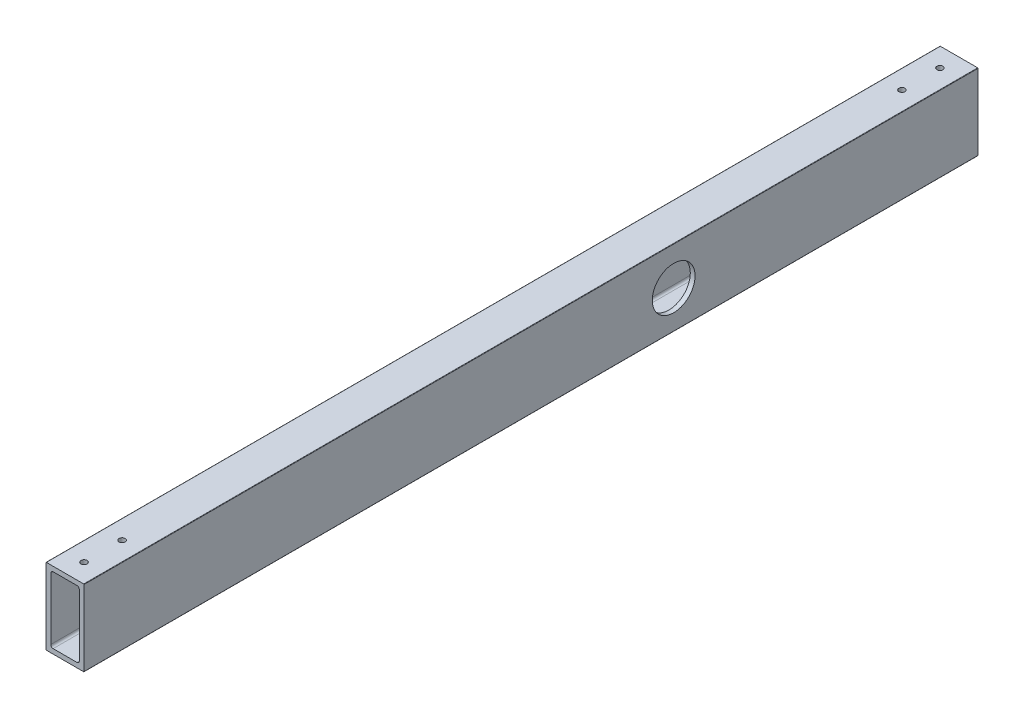
SolidWorks part; units mm, degrees
material "3.0205 (EN-AW 1200)"
ref_plane "Front Plane" through (0, 0, 0) normal (0, 0, 1) x (1, 0, 0)
ref_plane "Top Plane" through (0, 0, 0) normal (0, 1, 0) x (1, 0, 0)
ref_plane "Right Plane" through (0, 0, 0) normal (1, 0, 0) x (0, 0, -1)
ref_plane "Plane1" through (0, 0, 0) normal (0, 0, -1) x (-1, 0, 0)
sketch "Sketch1" plane through (0, 0, 0) normal (0, 0, -1) x (-1, 0, 0)
  line L0 (-3.175, 46.0375) -> (-3.175, 4.7625)
  line L1 (-4.7625, 3.175) -> (-20.6375, 3.175)
  line L2 (-22.225, 4.7625) -> (-22.225, 46.0375)
  line L3 (-20.6375, 47.625) -> (-4.7625, 47.625)
  line L4 (0, 0.254) -> (0, 50.546)
  line L5 (-0.254, 50.8) -> (-25.146, 50.8)
  line L6 (-25.4, 50.546) -> (-25.4, 0.254)
  line L7 (-25.146, 0) -> (-0.254, 0)
  arc A0 (-3.175, 4.7625) -> (-4.7625, 3.175) centre (-4.7625, 4.7625) cw
  arc A1 (-20.6375, 3.175) -> (-22.225, 4.7625) centre (-20.6375, 4.7625) cw
  arc A2 (-22.225, 46.0375) -> (-20.6375, 47.625) centre (-20.6375, 46.0375) cw
  arc A3 (-4.7625, 47.625) -> (-3.175, 46.0375) centre (-4.7625, 46.0375) cw
  arc A4 (-0.254, 0) -> (0, 0.254) centre (-0.254, 0.254) ccw
  arc A5 (0, 50.546) -> (-0.254, 50.8) centre (-0.254, 50.546) ccw
  arc A6 (-25.146, 50.8) -> (-25.4, 50.546) centre (-25.146, 50.546) ccw
  arc A7 (-25.4, 0.254) -> (-25.146, 0) centre (-25.146, 0.254) ccw
extrude "Boss-Extrude1" add sketch "Sketch1" against normal blind 596.9
sketch "Sketch2" plane through (0, 50.8, 0) normal (0, 1, 0) x (1, 0, 0)
  line L0 (0.254, -596.9) -> (25.146, -596.9) construction
  line L1 (25.146, -298.45) -> (0, -298.45) construction
  line L2 (25.146, -596.9) -> (25.146, 0) construction
  line L3 (0, -596.9) -> (0, 0) construction
  circle A0 centre (12.7, -584.2) radius 2.032
  circle A1 centre (12.7, -558.8) radius 2.032
  circle A2 centre (12.7, -38.1) radius 2.032
  circle A3 centre (12.7, -12.7) radius 2.032
  dimension "D1" = 4.064
  dimension "D2" = 4.064
  dimension "D3" = 12.7
  dimension "D4" = 25.4
extrude "Cut-Extrude1" cut sketch "Sketch2" against normal through all
ref_plane "Plane2" through (224.155, 46.0375, 596.9) normal (0, 0, -1) x (-1, 0, 0)
sketch "Sketch5" plane through (25.4, 0, 0) normal (1, 0, 0) x (0, 0, -1)
  line L0 (-596.9, 50.546) -> (0, 50.546) construction
  line L2 (0, 50.546) -> (0, 0.254) construction
  circle A0 centre (-203.2, 25.146) radius 14.2875
  dimension "D1" = 28.575
  dimension "D2" = 25.4
  dimension "D3" = 203.2
extrude "Cut-Extrude2" cut sketch "Sketch5" against normal through all
